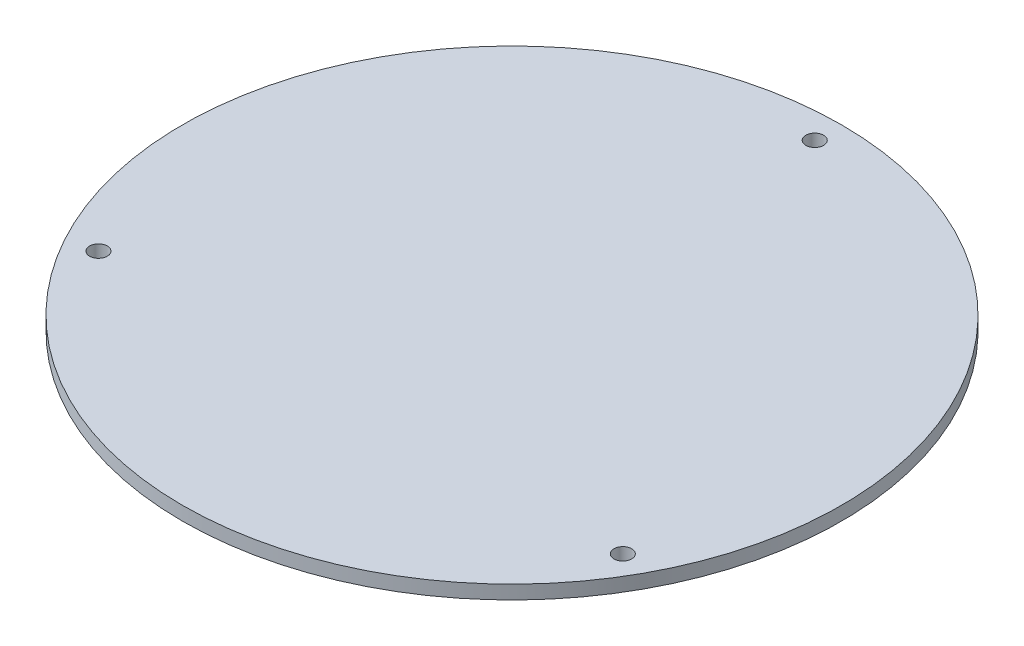
SolidWorks part; units mm, degrees
ref_plane "Front Plane" through (0, 0, 0) normal (0, 0, 1) x (1, 0, 0)
ref_plane "Top Plane" through (0, 0, 0) normal (0, 1, 0) x (1, 0, 0)
ref_plane "Right Plane" through (0, 0, 0) normal (1, 0, 0) x (0, 0, -1)
sketch "Sketch1" plane through (0, 0, 0) normal (0, 1, 0) x (1, 0, 0)
  circle A0 centre (0, 0) radius 152.4
  dimension "D1" = 304.8
extrude "Boss-Extrude1" add sketch "Sketch1" along normal blind 6.35
sketch "Sketch2" plane through (0, 6.35, 0) normal (0, 1, 0) x (1, 0, 0)
  line L0 (0, 0) -> (0, 140) construction
  circle A0 centre (0, 140) radius 4.1
  dimension "D2" = 8.2
  dimension "D1" = 140
extrude "Cut-Extrude1" cut sketch "Sketch2" against normal through all
pattern_circular "CirPattern1" count 3 every 120 about axis through (0, 6.35, 0) along (0, -1, 0) of "Cut-Extrude1"
